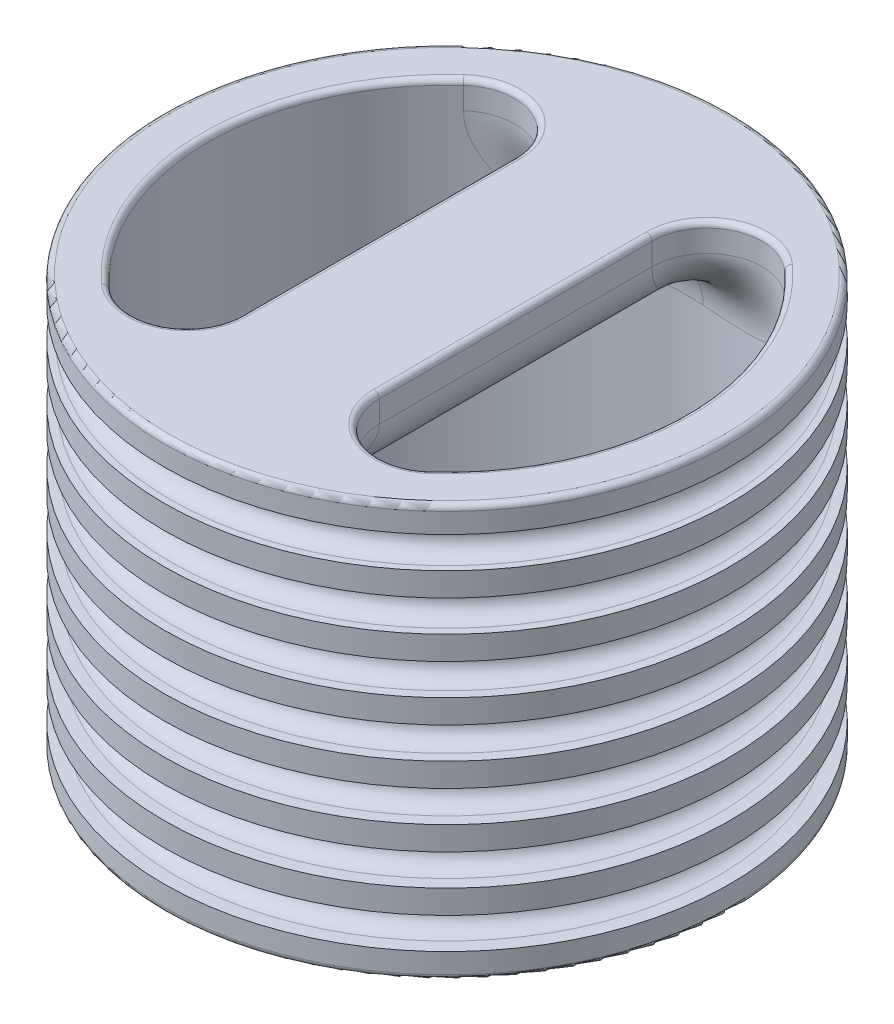
SolidWorks part; units mm, degrees
ref_plane "Front Plane" through (0, 0, 0) normal (0, 0, 1) x (1, 0, 0)
ref_plane "Top Plane" through (0, 0, 0) normal (0, 1, 0) x (1, 0, 0)
ref_plane "Right Plane" through (0, 0, 0) normal (1, 0, 0) x (0, 0, -1)
sketch "Sketch1" plane through (0, 0, 0) normal (0, 0, 1) x (1, 0, 0)
  line L0 (87, 75) -> (87, 0)
  line L1 (87, 0) -> (95, 0)
  line L2 (95, 0) -> (95, 75) construction
  line L3 (95, 75) -> (87, 75)
  line L4 (0, 0) -> (0, 75) construction
  line L5 (0, 75) -> (87, 75) construction
  line L6 (0, 0) -> (87, 0) construction
  line L7 (92.65, 7.5) -> (92.65, 17.5) construction
  line L8 (95.5, 75) -> (95.5, 0) construction
  line L9 (92.65, 17.5) -> (92.85, 17.5) construction
  line L10 (92.85, 17.5) -> (92.65, 7.5) construction
  line L11 (43.5, 75) -> (43.5, 0) construction
  line L12 (43.5, 37.5) -> (93.25, 37.5) construction
  line L13 (93.85, 70.35) -> (95, 70.35)
  line L14 (95, 70.35) -> (95, 75)
  line L15 (93.85, 64.65) -> (95, 64.65)
  line L16 (95, 64.65) -> (95, 60.35)
  line L17 (95, 60.35) -> (93.65, 60.35)
  line L18 (93.65, 54.65) -> (95, 54.65)
  line L19 (95, 54.65) -> (95, 50.35)
  line L20 (95, 50.35) -> (93.45, 50.35)
  line L21 (93.45, 44.65) -> (95, 44.65)
  line L22 (93.25, 40.35) -> (95, 40.35)
  line L23 (95, 40.35) -> (95, 44.65)
  line L24 (93.25, 34.65) -> (95, 34.65)
  line L25 (93.05, 30.35) -> (95, 30.35)
  line L26 (95, 30.35) -> (95, 34.65)
  line L27 (93.05, 24.65) -> (95, 24.65)
  line L28 (95, 24.65) -> (95, 20.35)
  line L29 (95, 20.35) -> (92.85, 20.35)
  line L30 (92.85, 14.65) -> (95, 14.65)
  line L31 (95, 14.65) -> (95, 10.35)
  line L32 (95, 10.35) -> (92.65, 10.35)
  line L33 (92.65, 4.65) -> (95, 4.65)
  line L34 (95, 4.65) -> (95, 0)
  arc A7 (92.65, 10.35) -> (92.65, 4.65) centre (92.65, 7.5) ccw
  arc A8 (92.85, 20.35) -> (92.85, 14.65) centre (92.85, 17.5) ccw
  arc A9 (93.05, 30.35) -> (93.05, 24.65) centre (93.05, 27.5) ccw
  arc A10 (93.25, 40.35) -> (93.25, 34.65) centre (93.25, 37.5) ccw
  arc A11 (93.45, 50.35) -> (93.45, 44.65) centre (93.45, 47.5) ccw
  arc A12 (93.65, 60.35) -> (93.65, 54.65) centre (93.65, 57.5) ccw
  arc A13 (93.85, 70.35) -> (93.85, 64.65) centre (93.85, 67.5) ccw
  point P8 (0, 0)
  point P10 (-95, 75)
  point P14 (-8.5, 75)
  point P16 (0, 0)
  point P18 (-8, 75)
  dimension "D1" = 5.7
  dimension "D2" = 103
  dimension "D3" = 8
  dimension "D4" = 75
  dimension "D5" = 10
  dimension "D6" = 104
  dimension "D8" = 7
  dimension "D7" = 0.2
revolve "Revolve1" add sketch "Sketch1" angle 360 about L11
sketch "Sketch2" plane through (0, 75, 0) normal (0, 1, 0) x (1, 0, 0)
  line L0 (31, 0) -> (56, 0) construction
  line L2 (31, 41.6653) -> (31, -41.6653)
  line L4 (56, 41.6653) -> (56, -41.6653)
  line L5 (43.5, 43.5) -> (43.5, -43.5) construction
  circle A1 centre (43.5, 0) radius 43.5 construction
  arc A2 (56, 41.6653) -> (31, 41.6653) centre (43.5, 0) ccw
  arc A3 (31, -41.6653) -> (56, -41.6653) centre (43.5, 0) ccw
  dimension "D1" = 25
extrude "Boss-Extrude1" add sketch "Sketch2" against normal blind 15
fillet "Fillet1" radius 10 8 edges at (31, 67.5, -41.6653) (56, 67.5, -41.6653) (56, 67.5, 41.6653) (31, 67.5, 41.6653) (43.5, 60, -43.5) (43.5, 60, 43.5) (56, 60, 0) (31, 60, 0)
fillet "Fillet2" radius 1 9 edges at (56, 75, 0) (31, 75, 0) (43.5, 0, 43.5) (25.0519, 75, -33.9617) (25.0519, 75, 33.9617) (61.9481, 75, 33.9617) (61.9481, 75, -33.9617) (0, 75, 0) (87, 75, 0)
fillet "Fillet3" radius 1 2 edges at (43.5, 0, 51.5) (43.5, 75, 51.5)
